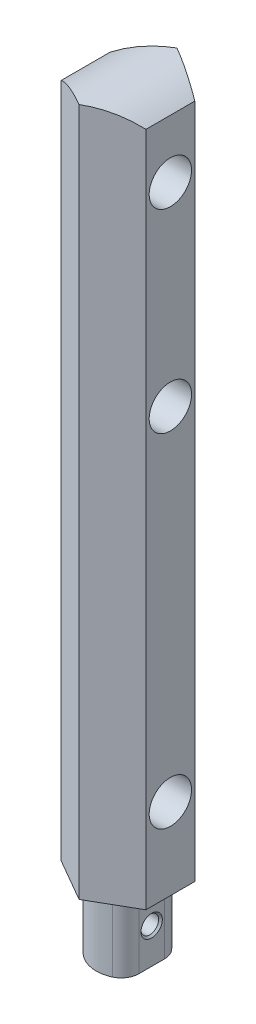
SolidWorks part; units mm, degrees
ref_plane "前视基准面" through (0, 0, 0) normal (0, 0, 1) x (1, 0, 0)
ref_plane "上视基准面" through (0, 0, 0) normal (0, 1, 0) x (1, 0, 0)
ref_plane "右视基准面" through (0, 0, 0) normal (1, 0, 0) x (0, 0, -1)
sketch "草图1" plane through (0, 0, 0) normal (0, 1, 0) x (1, 0, 0)
  line L1 (0, 13.8564) -> (-12, 6.9282)
  line L2 (-12, 6.9282) -> (-12, -6.9282)
  line L3 (-12, -6.9282) -> (0, -13.8564)
  line L4 (0, -13.8564) -> (12, -6.9282)
  line L5 (12, -6.9282) -> (12, 6.9282)
  line L6 (12, 6.9282) -> (0, 13.8564)
  circle A0 centre (0, 0) radius 13.8564 construction
  dimension "D1" = 24
extrude "凸台-拉伸1" add sketch "草图1" against normal blind 195
sketch "草图3" plane through (0, -195, 0) normal (0, -1, 0) x (1, 0, 0)
  line L0 (6.7, 3.6208) -> (6.7, -3.6208)
  arc A0 (3.825, 8.1467) -> (3.825, -8.1467) centre (0, 0) ccw
  arc A1 (3.825, -8.1467) -> (6.7, -3.6208) centre (1.7, -3.6208) ccw
  arc A2 (6.7, 3.6208) -> (3.825, 8.1467) centre (1.7, 3.6208) ccw
  dimension "D1" = 18
  dimension "D2" = 10
  dimension "D3" = 15.7
extrude "凸台-拉伸2" add sketch "草图3" along normal blind 20
sketch "草图5" plane through (0, 0, 0) normal (0, 0, 1) x (1, 0, 0)
  line L2 (-12, -3.5609) -> (-17.6784, -5.9246)
  line L3 (-12, -195) -> (-12, 0) construction
  line L5 (12, -195) -> (12, 0) construction
  line L6 (12, -3.5609) -> (25.3475, 18.4152)
  line L7 (25.3475, 18.4152) -> (-17.8887, 19.5529)
  line L8 (-17.8887, 19.5529) -> (-12, -3.5609)
  line L10 (0, -215) -> (0, 0)
  line L11 (-9, -215) -> (3.825, -215) construction
  arc A0 (12, -3.5609) -> (-12, -3.5609) centre (0, -22) ccw
  arc A1 (-12, -3.5609) -> (12, -3.5609) centre (0, -22) cw
  dimension "D1" = 22
  dimension "D3" = 215
  dimension "D2" = 112.6
extrude "切除-拉伸5" cut sketch "草图5" against normal blind 20 and the other way blind 20 contours A0 L6 L7 L8 region at (2.1036, 9.6975, 0)
hole_wizard "M6 螺纹孔1" positions "草图7" profile "草图9" tap size "M6" standard "GB" end condition through all
sketch "草图7" plane through (6.7, 0, 0) normal (1, 0, 0) x (0, 0, -1)
  line L0 (-6.9282, -195) -> (6.9282, -195) construction
  point P0 (0, -205)
  dimension "D1" = 10
sketch "草图9" plane through (6.7, -205, 0) normal (0, 1, 0) x (0, 0, -1)
  line L0 (0, 0) -> (0, 18.7)
  line L1 (0, 18.7) -> (2.5, 18.7)
  line L2 (2.5, 18.7) -> (2.5, 0.525)
  line L3 (2.5, 0.525) -> (3.025, 0)
  line L5 (3.025, 0) -> (0, 0)
  line L6 (-2.5, 0.525) -> (-3.025, 0) construction
  line L11 (0, -6.35) -> (0, 107.95) construction
  dimension "通孔螺纹孔钻头直径" = 5
  dimension "通孔螺纹孔钻头深度" = 18.7
  dimension "近端锥形沉头孔直径" = 6.05
  dimension "近端锥形沉头孔角度" = 90
cosmetic thread "孔螺蚊线1" parameters "D2"=6
hole_wizard "孔1" positions "草图10" profile "草图13" legacy
sketch "草图10" plane through (12, 0, 0) normal (1, 0, 0) x (0, 0, -1)
  line L0 (-6.9282, -195) -> (6.9282, -195) construction
  point P0 (0, -172)
  dimension "D1" = 23
sketch "草图13" plane through (12, -172, 0) normal (0, 1, 0) x (0, 0, -1)
  line L0 (0, 0) -> (0, 24)
  line L1 (0, 24) -> (3.25, 24)
  line L2 (3.25, 24) -> (3.25, 15)
  line L3 (3.25, 15) -> (6, 15)
  line L4 (6, 15) -> (6, 0)
  line L5 (6, 0) -> (0, 0)
  line L6 (0, 110) -> (0, -10) construction
  dimension "直径" = 6.5
  dimension "深度" = 24
  dimension "柱坑直径" = 12
  dimension "柱坑深度" = 15
hole_wizard "孔2" positions "草图14" profile "草图16" legacy end condition through all
sketch "草图14" plane through (12, 0, 0) normal (1, 0, 0) x (0, 0, -1)
  circle A0 centre (0, -172) radius 6 construction
  point P0 (0, -75)
  point P5 (0, -20)
  dimension "D1" = 97
  dimension "D2" = 55
sketch "草图16" plane through (12, -75, 0) normal (0, 1, 0) x (0, 0, -1)
  line L0 (0, 0) -> (0, 24)
  line L1 (0, 24) -> (3.25, 24)
  line L2 (3.25, 24) -> (3.25, 12)
  line L3 (3.25, 12) -> (6, 12)
  line L4 (6, 12) -> (6, 0)
  line L5 (6, 0) -> (0, 0)
  line L6 (0, 110) -> (0, -10) construction
  dimension "直径" = 6.5
  dimension "深度" = 24
  dimension "柱坑直径" = 12
  dimension "柱坑深度" = 12
